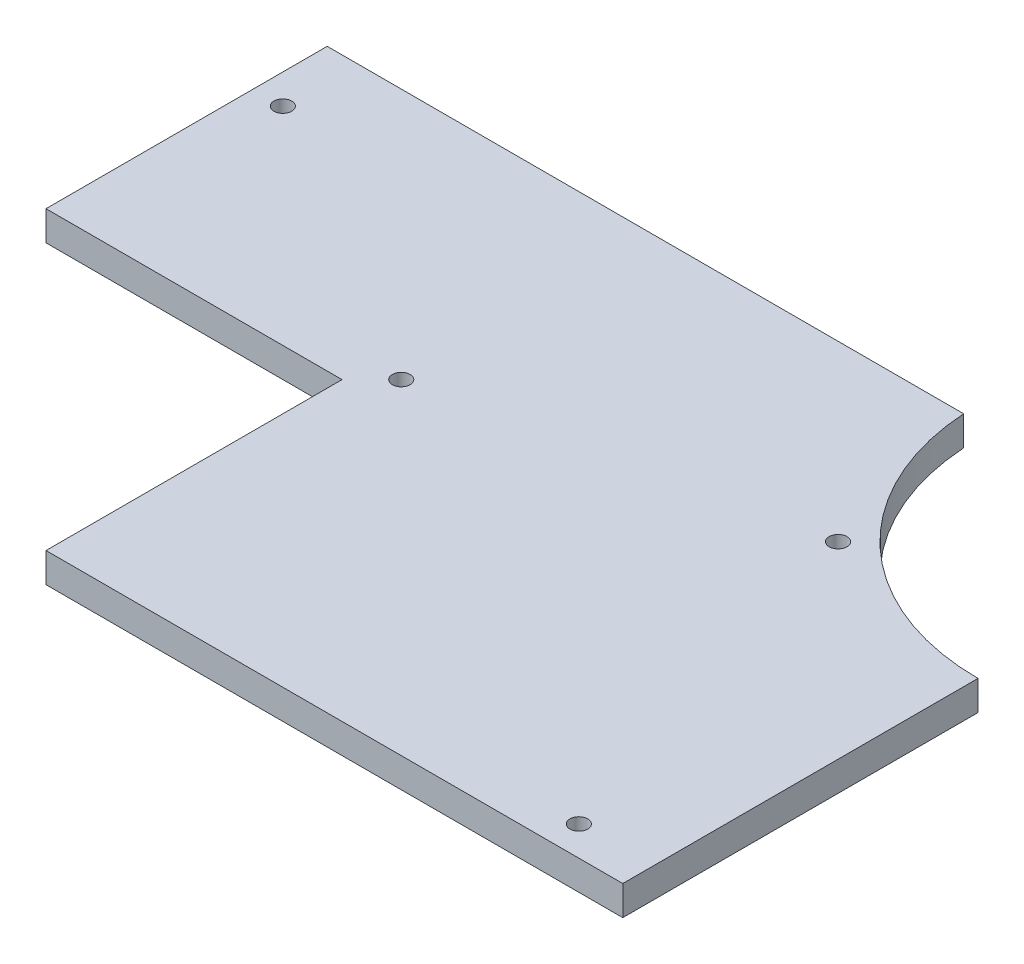
SolidWorks part; units mm, degrees
ref_plane "Plan de face" through (0, 0, 0) normal (0, 0, 1) x (1, 0, 0)
ref_plane "Plan de dessus" through (0, 0, 0) normal (0, 1, 0) x (1, 0, 0)
ref_plane "Plan de droite" through (0, 0, 0) normal (1, 0, 0) x (0, 0, -1)
sketch "Esquisse1" plane through (0, 0, 0) normal (0, 1, 0) x (1, 0, 0)
  line L1 (0, -97.415) -> (-97.415, -97.415)
  line L4 (-147.415, -47.415) -> (-147.415, 2.585)
  line L9 (-147.415, 2.585) -> (0, 2.585) construction
  line L14 (-147.415, -47.415) -> (-97.415, -47.415)
  line L15 (-97.415, -47.415) -> (-97.415, -97.415)
  line L16 (-92.415, -92.415) -> (-3.9118, -92.415) construction
  line L17 (-147.415, -42.415) -> (-92.415, -42.415) construction
  line L18 (-92.415, -42.415) -> (-92.415, -97.415) construction
  line L19 (0, 2.585) -> (-31.8198, -29.2348) construction
  line L20 (-147.415, 0.085) -> (-0.1286, 0.085)
  line L21 (0, -97.415) -> (0, 2.585)
  line L27 (-142.415, 2.585) -> (-142.415, -47.415) construction
  circle A3 centre (-142.415, -42.415) radius 1.5 construction
  circle A4 centre (-92.415, -42.415) radius 1.5
  circle A5 centre (-92.415, -92.415) radius 1.5 construction
  circle A14 centre (-142.415, -12.415) radius 1.5
  circle A15 centre (-12.415, -92.415) radius 1.5
  arc A16 (-40, 2.585) -> (0, -37.415) centre (0, 2.585) ccw
  circle A18 centre (-31.8198, -29.2348) radius 1.5
  point P0 (0, 0)
  dimension "D7" = 30
  dimension "D2" = 3
  dimension "D12" = 40
  dimension "D3" = 45
  dimension "D4" = 5
  dimension "D5" = 5
  dimension "D6" = 5
  dimension "D8" = 80
  dimension "D9" = 5
  dimension "D10" = 50
  dimension "D11" = 97.415
  dimension "D13" = 45
  dimension "D15" = 5
extrude "Boss.-Extru.1" add sketch "Esquisse1" along normal blind 5 contours L14 L15 L1 L9 L4 A5 A4 A3 region at (-68.4927, 0, 46.6839)
